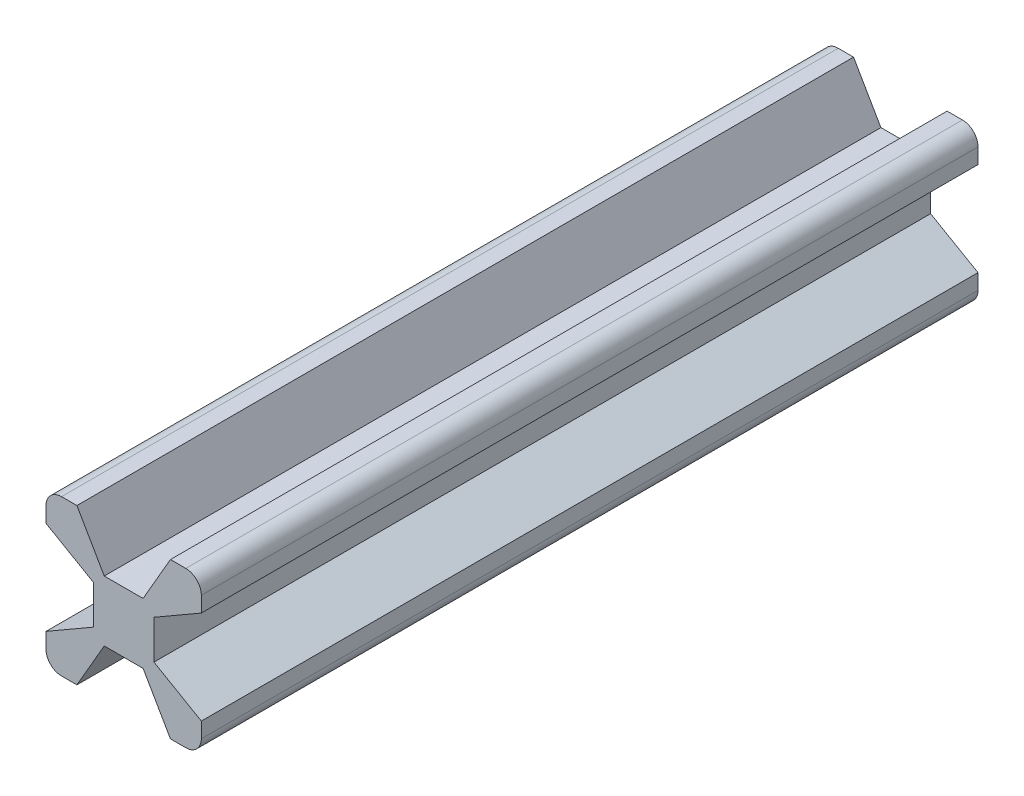
SolidWorks part; units mm, degrees
ref_plane "Front Plane" through (0, 0, 0) normal (0, 0, 1) x (1, 0, 0)
ref_plane "Top Plane" through (0, 0, 0) normal (0, 1, 0) x (1, 0, 0)
ref_plane "Right Plane" through (0, 0, 0) normal (1, 0, 0) x (0, 0, -1)
sketch "Sketch1" plane through (0, 0, 0) normal (0, 0, 1) x (1, 0, 0)
  line L5 (10, -10) -> (-10, -10)
  line L6 (10, -10) -> (10, 10)
  line L7 (10, 10) -> (-10, 10)
  line L8 (-10, -10) -> (-10, 10)
  line L9 (10, -10) -> (-10, 10) construction
  line L10 (10, 10) -> (-10, -10) construction
  point P0 (0, 0)
  dimension "D1" = 20
  dimension "D2" = 20
extrude "Boss-Extrude1" add sketch "Sketch1" along normal blind 100
ref_axis "Axis1" through (0, 0, -5) along (0, 0, 1)
sketch "Sketch2" plane through (0, 0, 0) normal (0, 0, 1) x (1, 0, 0)
  line L0 (-6.0218, 10) -> (-2.5, 3.9)
  line L1 (-2.5, 3.9) -> (2.5, 3.9)
  line L2 (2.5, 3.9) -> (6.0218, 10)
  line L4 (-10, 10) -> (-10, -10)
  line L5 (-10, 10) -> (-10, -10)
  line L6 (10, 10) -> (-10, 10)
  line L7 (-10, -10) -> (10, -10)
  line L10 (10, 10) -> (-10, 10)
  line L15 (-10, -10) -> (10, -10)
  line L16 (10, -10) -> (10, 10)
  line L17 (10, -10) -> (10, 10)
  point P0 (0, 0)
  point P7 (0, 3.9)
  dimension "D2" = 120
  dimension "D3" = 5
  dimension "D4" = 6.1
  dimension "D1" = 0
extrude "Cut-Extrude1" cut sketch "Sketch2" along normal through all contours L2 L0 L1 region at (0, 7.3702, 0)
pattern_circular "CirPattern1" count 4 over 360 about axis through (0, 0, -5) along (0, 0, 1) of "Cut-Extrude1"
fillet "Fillet1" radius 2 4 edges at (-10, -10, 50) (10, -10, 50) (10, 10, 50) (-10, 10, 50)
